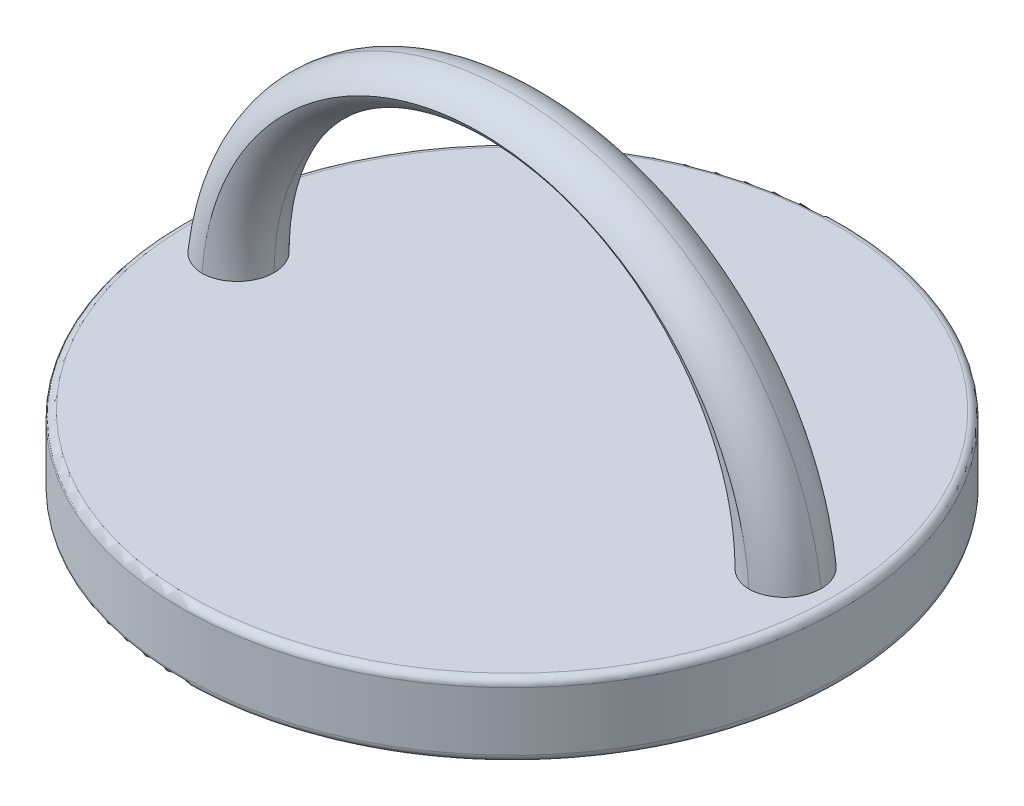
SolidWorks part; units mm, degrees
ref_plane "Front Plane" through (0, 0, 0) normal (0, 0, 1) x (1, 0, 0)
ref_plane "Top Plane" through (0, 0, 0) normal (0, 1, 0) x (1, 0, 0)
ref_plane "Right Plane" through (0, 0, 0) normal (1, 0, 0) x (0, 0, -1)
sketch "Sketch1" plane through (0, 0, 0) normal (0, 0, 1) x (1, 0, 0)
  line L1 (0, 0) -> (45, 0)
  line L2 (0, 0) -> (0, -10)
  line L3 (0, -10) -> (45, -10)
  line L4 (45, 0) -> (45, -10)
  line L5 (0, -10) -> (43, -10)
  line L6 (0, -10) -> (0, -5)
  line L7 (0, -5) -> (41, -5)
  line L8 (43, -10) -> (43, -7)
  arc A0 (41, -5) -> (43, -7) centre (41, -7) cw
  point P11 (43, -5)
  dimension "D5" = 2
  dimension "D1" = 45
  dimension "D2" = 10
  dimension "D3" = 43
  dimension "D4" = 5
revolve "Revolve1" add sketch "Sketch1" angle 360 about L2 region at (23.4845, -2.7227, 0)
ref_plane "Plane1" through (0, 0, 5) normal (0, 0, 1) x (1, 0, 0)
sketch "Sketch2" plane through (0, 0, 5) normal (0, 0, 1) x (1, 0, 0)
  line L0 (45, 0) -> (-45, 0) construction
  line L1 (0, 0) -> (0, -10) construction
  line L2 (-45, -10) -> (45, -10) construction
  line L3 (-43.1403, 0) -> (42.4806, 0)
  circle A0 centre (0, 0) radius 32.5
  circle A1 centre (0, -5) radius 42.5
  dimension "D1" = 65
  dimension "D2" = 85
  dimension "D3" = 5
extrude "Boss-Extrude1" add sketch "Sketch2" against normal blind 10 contours L3 A1 A0 region at (0, 36.5764, 5)
fillet "Fillet1" radius 5 4 edges at (0, 32.5, -5) (0, 32.5, 5) (0, 37.5, -5) (0, 37.5, 5)
fillet "Fillet2" radius 1 3 edges at (-45, 0, 0) (-45, -10, 0) (-43, -10, 0)
